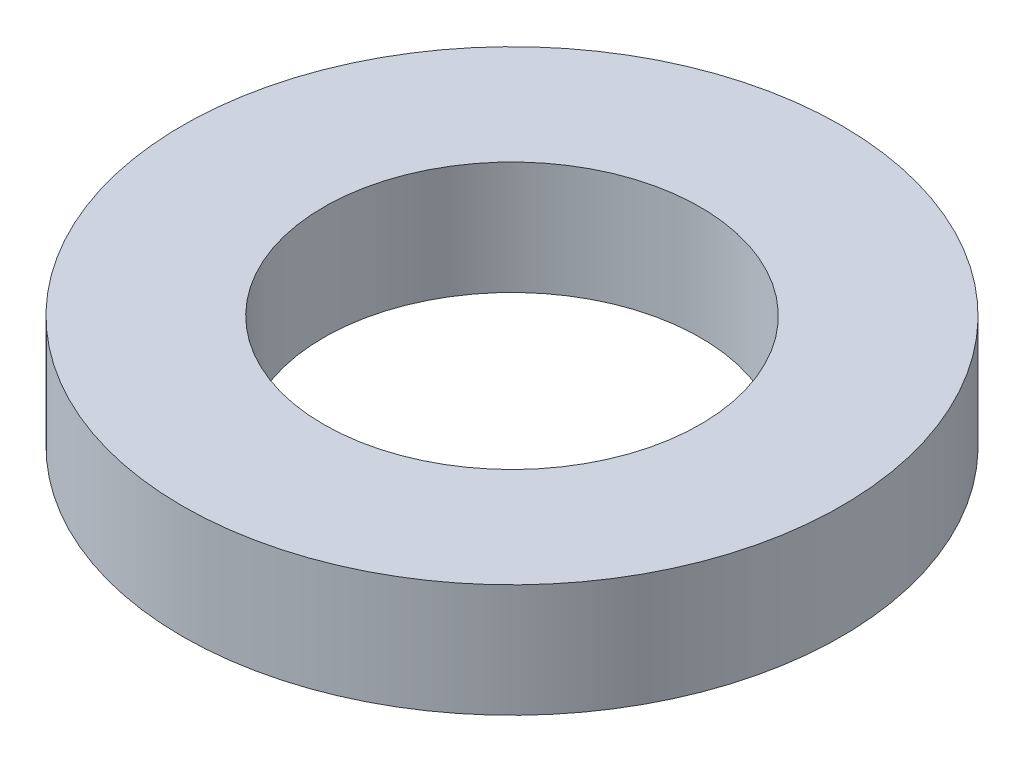
SolidWorks part; units mm, degrees
ref_plane "Front Plane" through (0, 0, 0) normal (0, 0, 1) x (1, 0, 0)
ref_plane "Top Plane" through (0, 0, 0) normal (0, 1, 0) x (1, 0, 0)
ref_plane "Right Plane" through (0, 0, 0) normal (1, 0, 0) x (0, 0, -1)
sketch "Sketch1" plane through (0, 0, 0) normal (0, 1, 0) x (1, 0, 0)
  circle A0 centre (0, 0) radius 87.5
  dimension "FLANGE_OD" = 175
extrude "Boss-Extrude1" add sketch "Sketch1" along normal blind 30
sketch "Sketch2" plane through (0, 0, 0) normal (0, 1, 0) x (1, 0, 0)
  circle A0 centre (0, 0) radius 50
  dimension "BORE_D" = 100
extrude "Cut-Extrude1" cut sketch "Sketch2" along normal through all
sketch "Sketch3" plane through (0, 30, 0) normal (0, 1, 0) x (1, 0, 0)
  circle A0 centre (0, 0) radius 29.7939 construction
  circle A1 centre (-29.7939, 0) radius 6.7165
  dimension "BOLT_D" = 13.433
  dimension "BOLT_PCD" = 59.5877
extrude "Cut-Extrude2" cut sketch "Sketch3" against normal blind 19.2216 rebuild error yes
pattern_circular "CirPattern1" count 5 over 360 rebuild error yes
